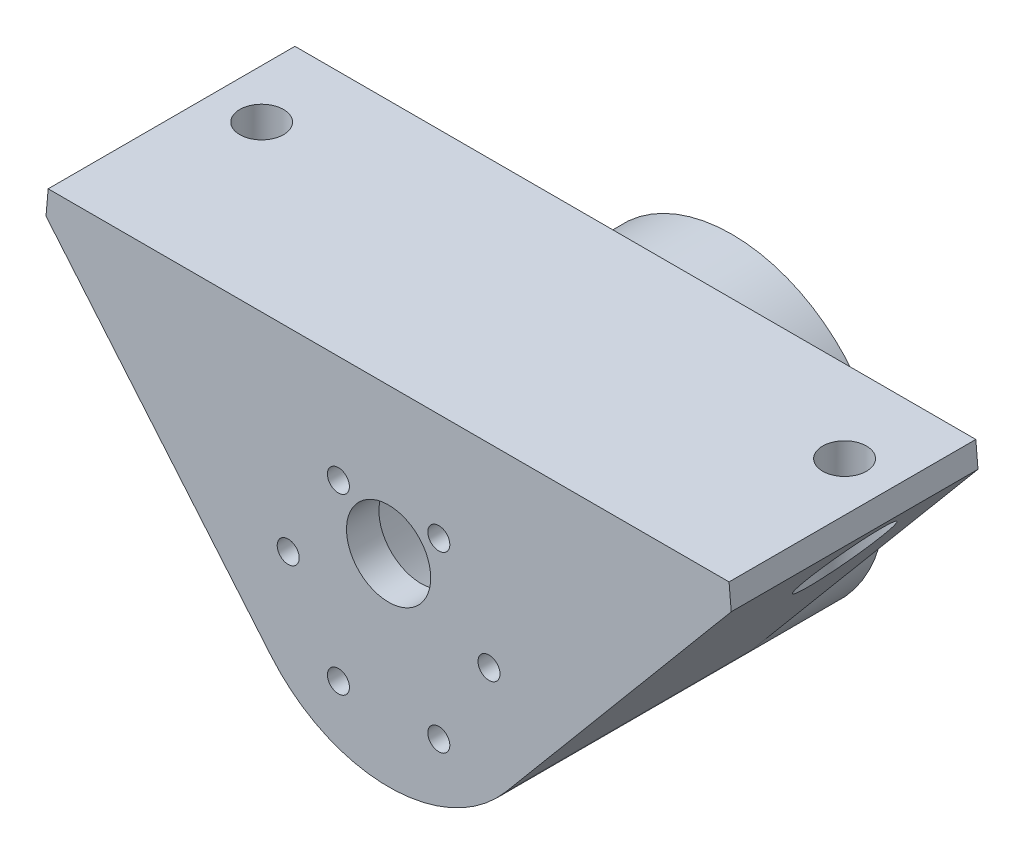
SolidWorks part; units mm, degrees
ref_plane "Front Plane" through (0, 0, 0) normal (0, 0, 1) x (1, 0, 0)
ref_plane "Top Plane" through (0, 0, 0) normal (0, 1, 0) x (1, 0, 0)
ref_plane "Right Plane" through (0, 0, 0) normal (1, 0, 0) x (0, 0, -1)
sketch "Sketch1" plane through (0, 0, 0) normal (0, 0, 1) x (1, 0, 0)
  circle A0 centre (0, 0) radius 15.5
  circle A1 centre (0, 0) radius 18.7
  circle A2 centre (0, 7.5) radius 6.5
  circle A3 centre (0, 0) radius 23.7
  dimension "D1" = 31
  dimension "D2" = 37.4
  dimension "D3" = 13
  dimension "D4" = 7.5
  dimension "D5" = 5
extrude "Boss-Extrude1" add sketch "Sketch1" against normal blind 48 contours A3 A1 region at (-23.0297, 0, 0)
extrude "Boss-Extrude2" add sketch "Sketch1<3>" along normal blind 5 contours A3 A1 | A1 A0 | A0 A2 region at (0, -1.6004, 0) region at (-18.1711, 0, 0) region at (-23.0297, 0, 0)
sketch "Sketch1<3>" plane through (0, 0, 0) normal (0, 0, 1) x (1, 0, 0) same geometry as "Sketch1"
sketch "Sketch2" plane through (0, 0, 5) normal (0, 0, 1) x (1, 0, 0)
  line L0 (0, 0) -> (-15.5, 0) construction
  circle A0 centre (0, 0) radius 15.5 construction
  circle A1 centre (0, 0) radius 15.5 construction
  point P4 (-15.5, 0)
hole_wizard "M3 Clearance Hole1" positions "Sketch2" profile "Sketch3" hole size "M3" standard "ANSI Metric" end condition through all
sketch "Sketch3" plane through (-15.5, 0, 5) normal (1, 0, 0) x (0, -1, 0)
  line L0 (0, 0) -> (0, 53)
  line L1 (0, 53) -> (1.7, 53)
  line L2 (1.7, 53) -> (1.7, 0)
  line L5 (1.7, 0) -> (0, 0)
  line L11 (0, -6.35) -> (0, 107.95) construction
  dimension "Thru Hole Dia." = 3.4
  dimension "Thru Hole Depth" = 53
pattern_circular "CirPattern1" count 6 over 360 about axis through (0, 0, -48) along (0, 0, 1) of "M3 Clearance Hole1" reverse direction yes
sketch "Sketch5" plane through (0, 0, 5) normal (0, 0, 1) x (1, 0, 0)
  line L0 (-56.1111, 30) -> (56.1111, 30)
  line L1 (-56.1111, 30) -> (-18.1553, -15.2341)
  line L2 (56.1111, 30) -> (18.1553, -15.2341)
  circle A0 centre (0, 0) radius 23.7 construction
  circle A1 centre (0, 0) radius 23.7
  circle M11 centre (0, 0) radius 23.7
  dimension "D1" = 30
  dimension "D2" = 50
extrude "Boss-Extrude3" add sketch "Sketch5" against normal blind 38.1 contours L2 L0 L1 M11 region at (0, 28.79, 5)
sketch "Sketch6" plane through (0, 30, 0) normal (0, 1, 0) x (1, 0, 0)
  line L0 (-45, 20.4) -> (45, 20.4) construction
  line L2 (-56.1111, -5) -> (56.1111, -5) construction
  point P3 (0, 20.4)
  dimension "D1" = 90
  dimension "D2" = 25.4
hole_wizard "1/4 Clearance Hole1" positions "Sketch7" profile "Sketch8" hole size "1/4" standard "ANSI Inch" end condition through all
sketch "Sketch7" plane through (0, 30, 0) normal (0, 1, 0) x (1, 0, 0)
  point P0 (-45, 20.4)
  point P3 (45, 20.4)
sketch "Sketch8" plane through (-45, 30, -20.4) normal (1, 0, 0) x (0, 0, 1)
  line L0 (0, 0) -> (0, 53.7)
  line L1 (0, 53.7) -> (3.3782, 53.7)
  line L2 (3.3782, 53.7) -> (3.3782, 0)
  line L5 (3.3782, 0) -> (0, 0)
  line L11 (0, -6.35) -> (0, 107.95) construction
  dimension "Thru Hole Dia." = 6.7564
  dimension "Thru Hole Depth" = 53.7
ref_plane "Plane2" through (0, 25, 0) normal (0, 1, 0) x (1, 0, 0)
sketch "Sketch9" plane through (0, 25, 0) normal (0, 1, 0) x (1, 0, 0)
  circle A0 centre (-45, 20.4) radius 5.715
  circle A1 centre (45, 20.4) radius 5.715
  dimension "D1" = 11.43
extrude "Cut-Extrude1" cut sketch "Sketch9" against normal through all
chamfer "Chamfer1" distance 5 angle 45 2 edges at (56.1111, 30, -14.05) (-56.1111, 30, -14.05) first distance on face at (50.715, 23.5691, -20.4) first distance on face at (-50.715, 23.5691, -20.4)
